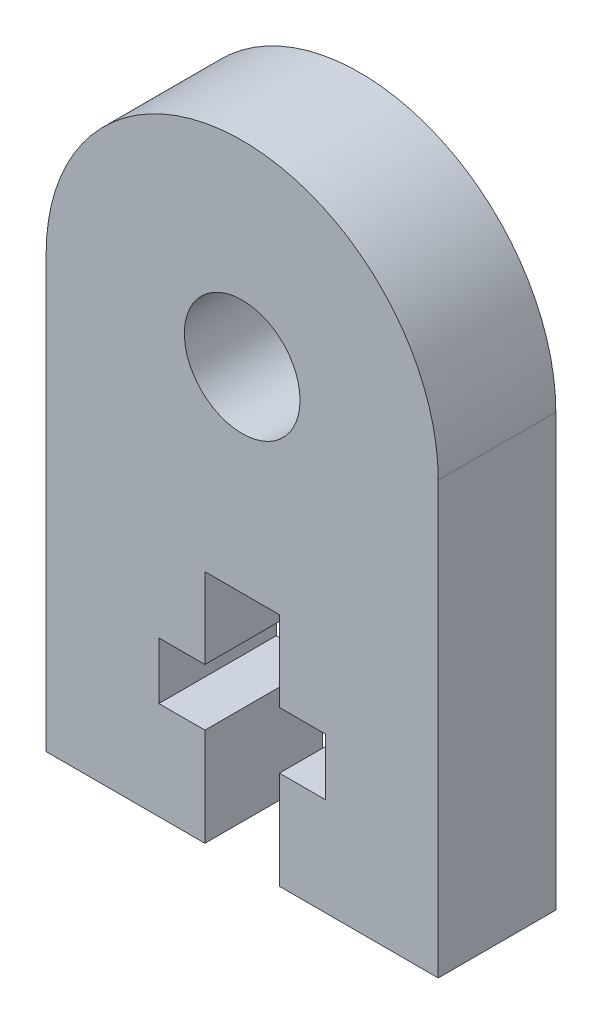
SolidWorks part; units mm, degrees
material "ABS"
ref_plane "Front Plane" through (0, 0, 0) normal (0, 0, 1) x (1, 0, 0)
ref_plane "Top Plane" through (0, 0, 0) normal (0, 1, 0) x (1, 0, 0)
ref_plane "Right Plane" through (0, 0, 0) normal (1, 0, 0) x (0, 0, -1)
sketch "Sketch1" plane through (0, 0, 0) normal (0, 0, 1) x (1, 0, 0)
  line L0 (0, 0) -> (-2.086, 2.086) construction
  line L1 (0, 0) -> (0, 2.95) construction
  line L2 (-10, 0) -> (-10, -22)
  line L3 (-10, -22) -> (10, -22)
  line L4 (10, -22) -> (10, 0)
  line L5 (0, 0) -> (0, -22) construction
  circle A0 centre (0, 0) radius 2.95
  arc A1 (-10, 0) -> (10, 0) centre (0, 0) cw
  dimension "D1" = 5.9
  dimension "D4" = 45
  dimension "D5" = 22
  dimension "D6" = 20
extrude "Boss-Extrude1" add sketch "Sketch1" along normal blind 6
sketch "Sketch3" plane through (0, 0, 6) normal (0, 0, 1) x (1, 0, 0)
  line L0 (-10, -22) -> (10, -22) construction
  line L1 (-1.9, -22) -> (1.9, -22)
  line L2 (-1.9, -22) -> (-1.9, -17)
  line L3 (-1.9, -10) -> (1.9, -10)
  line L4 (1.9, -22) -> (1.9, -17)
  line L5 (0, -10) -> (0, 0) construction
  line L6 (1.9, -14.1) -> (4.25, -14.1)
  line L7 (-4.25, -14.1) -> (-1.9, -14.1)
  line L8 (-4.25, -14.1) -> (-4.25, -17)
  line L9 (-4.25, -17) -> (-1.9, -17)
  line L10 (4.25, -14.1) -> (4.25, -17)
  line L11 (-1.9, -14.1) -> (-1.9, -10)
  line L12 (1.9, -17) -> (4.25, -17)
  line L13 (1.9, -14.1) -> (1.9, -10)
  point P18 (-3.075, -17)
  dimension "D1" = 3.8
  dimension "D3" = 12
  dimension "D4" = 8.5
  dimension "D5" = 2.9
  dimension "D6" = 5
extrude "Cut-Extrude2" cut sketch "Sketch3" against normal through all
equation "\"smallPulleyTeeth\"= 15"
equation "\"largePulleyTeeth\"= 30"
equation "\"eighthThick\"= 2.9mm"
equation "\"sixteenthThick\" = 1.7mm"
equation "\"quarterThick\"=6.0mm"
equation "\"OD\" = 145mm"
equation "\"puckAngle\" = 60.5deg"
equation "\"puckDiam\" = 76.5mm"
equation "\"axlePress\" = 5.9mm"
equation "\"D1@Sketch1\"=\"axlePress\""
equation "\"D1@Boss-Extrude1\"=\"quarterThick\""
equation "\"press\" = 0.2mm"
equation "\"wheelClear\" = 0.3mm"
equation "\"10-32clear\" = 4.8mm"
equation "\"D1@Sketch3\"=\"8-32clear\"-\"press\""
equation "\"6-32clear\" = 3.3mm"
equation "\"8-32clear\" = 4.0mm"
equation "\"wheelHeight\" = 22mm"
equation "\"D5@Sketch1\"=\"wheelHeight\""
equation "\"wheelWell\" = 65mm"
